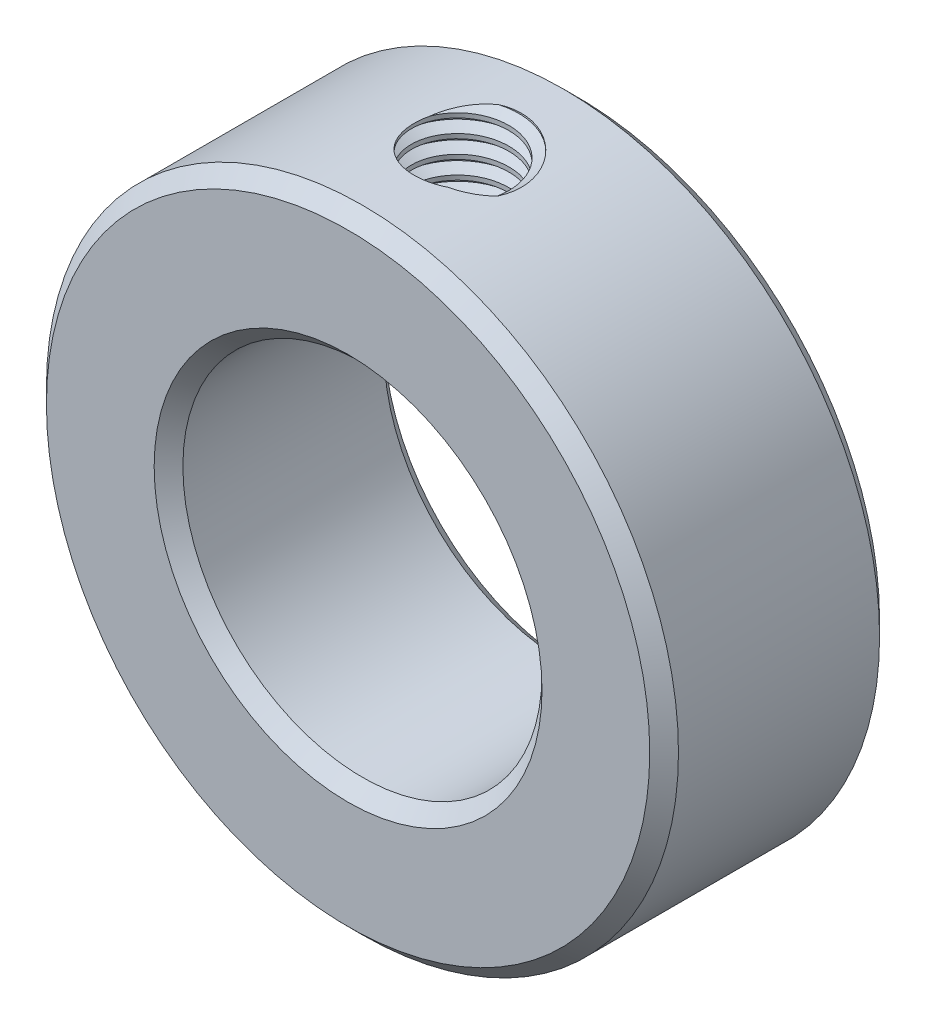
SolidWorks part; units mm, degrees
material "AISI 1020"
ref_plane "Front Plane" through (0, 0, 0) normal (0, 0, 1) x (1, 0, 0)
ref_plane "Top Plane" through (0, 0, 0) normal (0, 1, 0) x (1, 0, 0)
ref_plane "Right Plane" through (0, 0, 0) normal (1, 0, 0) x (0, 0, -1)
sketch "Sketch2" plane through (0, 0, 0) normal (0, 0, 1) x (1, 0, 0)
  circle A0 centre (0, 0) radius 22
  circle A1 centre (0, 0) radius 12.5
  dimension "D1" = 44
  dimension "D2" = 25
extrude "Boss-Extrude1" add sketch "Sketch2" along normal blind 16
ref_plane "Plane1" through (0, 22, 0) normal (0, 1, 0) x (1, 0, 0)
sketch "Sketch3" plane through (0, 22, 0) normal (0, 1, 0) x (1, 0, 0)
  line L0 (12.5, 0) -> (-12.5, 0) construction
  circle A0 centre (0, -8) radius 3.4
  dimension "D1" = 6.8
  dimension "D2" = 8
extrude "Cut-Extrude1" cut sketch "Sketch3" against normal up to next
chamfer "Chamfer1" distance 1 angle 45 4 edges at (12.5, 0, 0) (22, 0, 0) (12.5, 0, 16) (22, 0, 16)
thread "Thread1" pitch 1.25 method cut profile "Thread Profile1" start angle 0, offset 2, length 15, pitch 1.25, diameter 6.8
ref_plane "Plane2" through (-3.4, 24, 8) normal (0, 0, 1) x (-1, 0, 0)
sketch "Thread Profile1" plane through (-3.4, 24, 8) normal (0, 0, 1) x (-1, 0, 0)
  line L0 (0, 0) -> (0, 1.25) construction
  line L1 (0, 0) -> (0.6766, 0.3906)
  line L2 (0.6766, 0.3906) -> (0.6766, 0.5469)
  line L3 (0.6766, 0.5469) -> (0, 0.9375)
  line L4 (0.6766, 0.4687) -> (0, 0.4687) construction
  line L11 (0, 0) -> (0, 0.9375)
  point P2 (0, 0)
  dimension "Pitch" = 1.25
  dimension "Profile_Angle" = 60
  dimension "Profile_Land" = 0.1562
  dimension "Profile_Height" = 0.6766
